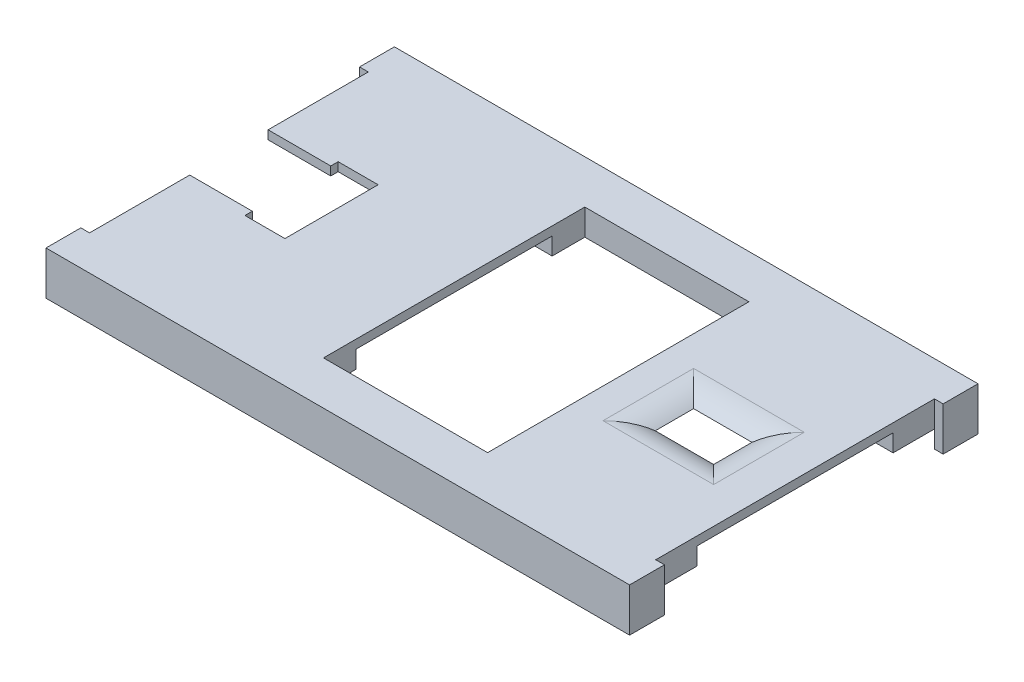
SolidWorks part; units mm, degrees
ref_plane "Front Plane" through (0, 0, 0) normal (0, 0, 1) x (1, 0, 0)
ref_plane "Top Plane" through (0, 0, 0) normal (0, 1, 0) x (1, 0, 0)
ref_plane "Right Plane" through (0, 0, 0) normal (1, 0, 0) x (0, 0, -1)
sketch "Sketch1" plane through (0, 0, 0) normal (0, 1, 0) x (1, 0, 0)
  line L0 (65, -38) -> (65, -40)
  line L1 (2, 0) -> (63, 0)
  line L2 (0, -2) -> (0, -38)
  line L3 (2, -40) -> (63, -40)
  line L4 (65, -2) -> (65, -38)
  line L5 (65, -40) -> (63, -40)
  line L6 (0, -38) -> (0, -40)
  line L7 (0, -40) -> (2, -40)
  line L8 (2, 0) -> (0, 0)
  line L9 (0, 0) -> (0, -2)
  line L10 (65, -2) -> (65, 0)
  line L11 (65, 0) -> (63, 0)
  point P9 (65, -40)
  point P12 (65, 0)
  point P15 (0, 0)
  dimension "D1" = 65
  dimension "D2" = 40
extrude "Boss-Extrude1" add sketch "Sketch1" along normal blind 3
sketch "Sketch2" plane through (0, 3, 0) normal (0, 1, 0) x (1, 0, 0)
  line L0 (51.65, -21.7) -> (57.35, -21.7) construction
  line L1 (51.65, -18.3) -> (57.35, -18.3) construction
  line L2 (51.65, -18.3) -> (51.65, -21.7) construction
  line L3 (51.65, -21.7) -> (57.35, -21.7) construction
  line L4 (57.35, -18.3) -> (57.35, -21.7) construction
  line L5 (57.35, -21.7) -> (57.35, -18.3) construction
  line L6 (51.15, -17.8) -> (57.85, -17.8)
  line L7 (57.85, -17.8) -> (57.85, -22.2)
  line L8 (51.15, -22.2) -> (57.85, -22.2)
  line L9 (51.15, -17.8) -> (51.15, -22.2)
  line L10 (11.28, -15.15) -> (9.08, -15.15) construction
  line L11 (11.28, -24.85) -> (7.69, -24.85) construction
  line L12 (11.28, -24.85) -> (11.28, -15.15) construction
  line L13 (11.28, -15.15) -> (7.69, -15.15) construction
  line L14 (7.69, -24.85) -> (7.69, -15.15) construction
  line L16 (11.78, -25.35) -> (7.19, -25.35)
  line L18 (7.19, -25.35) -> (7.19, -24.5)
  line L19 (11.78, -14.65) -> (7.19, -14.65)
  line L20 (11.78, -25.35) -> (11.78, -14.65)
  line L23 (7.19, -17.06) -> (7.19, -22.94) construction
  line L24 (-0.16, -24.5) -> (7.19, -24.5) construction
  line L25 (7.19, -24.5) -> (-0.16, -24.5)
  line L27 (7.19, -15.5) -> (-0.16, -15.5)
  line L28 (-0.16, -24.5) -> (-0.16, -15.5)
  line L29 (7.19, -15.5) -> (7.19, -14.65)
  line L30 (7.19, -25.35) -> (7.19, -14.65) construction
  line L31 (65, 0) -> (0, 0) construction
  line L32 (25.86, -5) -> (44.7, -5)
  line L33 (25.86, -5) -> (25.86, -35)
  line L34 (25.86, -35) -> (44.7, -35)
  line L35 (44.7, -5) -> (44.7, -35)
  line L36 (0, -40) -> (65, -40) construction
  line L37 (23.86, -29) -> (23.86, -11) construction
  line L38 (46.7, -24.37) -> (46.7, -29) construction
  dimension "D3" = 5
  dimension "D4" = 5
  dimension "D5" = 2
  dimension "D6" = 2
  dimension "D1" = 0.5
  dimension "D2" = 0.5
extrude "Cut-Extrude1" cut sketch "Sketch2" against normal through all
sketch "Sketch5" plane through (44.7, 0, 0) normal (-1, 0, 0) x (0, 0, 1)
  line L2 (0, 0) -> (15.5, 0) construction
  line L3 (8.75, 0) -> (31.25, 0)
  line L11 (8.75, 0) -> (8.75, 2)
  line L12 (8.75, 2) -> (31.25, 2)
  line L13 (31.25, 0) -> (31.25, 2)
  line L14 (40, 3) -> (40, 0) construction
  line L15 (0, 3) -> (0, 0) construction
  dimension "D1" = 2
  dimension "D2" = 8.75
  dimension "D3" = 8.75
extrude "Cut-Extrude2" cut sketch "Sketch5" against normal through all and the other way through all
fillet "Fillet3" radius 5 4 edges at (54.5, 3, 22.2) (57.85, 3, 20) (54.5, 3, 17.8) (51.15, 3, 20)
sketch "Sketch8" plane through (0, 3, 0) normal (0, 1, 0) x (1, 0, 0)
  line L0 (-1, -40) -> (66, -40)
  line L1 (66, -40) -> (66, -39)
  line L2 (65, -39) -> (0, -39)
  line L3 (-1, -39) -> (-1, -40)
  line L4 (-1, 0) -> (66, 0)
  line L5 (66, 0) -> (66, -1)
  line L6 (65, -1) -> (0, -1)
  line L7 (-1, -1) -> (-1, 0)
  line L8 (0, 0) -> (0, -40) construction
  line L9 (65, -40) -> (65, 0) construction
  line L10 (-1, -1) -> (-1, -4)
  line L11 (-1, -4) -> (0, -4)
  line L12 (0, -4) -> (0, -1)
  line L13 (66, -1) -> (66, -4)
  line L14 (66, -4) -> (65, -4)
  line L15 (65, -4) -> (65, -1)
  line L16 (-1, -39) -> (-1, -36)
  line L17 (-1, -36) -> (0, -36)
  line L18 (0, -36) -> (0, -39)
  line L19 (66, -39) -> (66, -36)
  line L20 (66, -36) -> (65, -36)
  line L21 (65, -36) -> (65, -39)
  dimension "D1" = 1
  dimension "D2" = 1
  dimension "D3" = 1
  dimension "D4" = 1
  dimension "D5" = 1
  dimension "D6" = 1
  dimension "D7" = 3
  dimension "D8" = 3
  dimension "D9" = 3
extrude "Boss-Extrude2" add sketch "Sketch8" against normal blind 5
